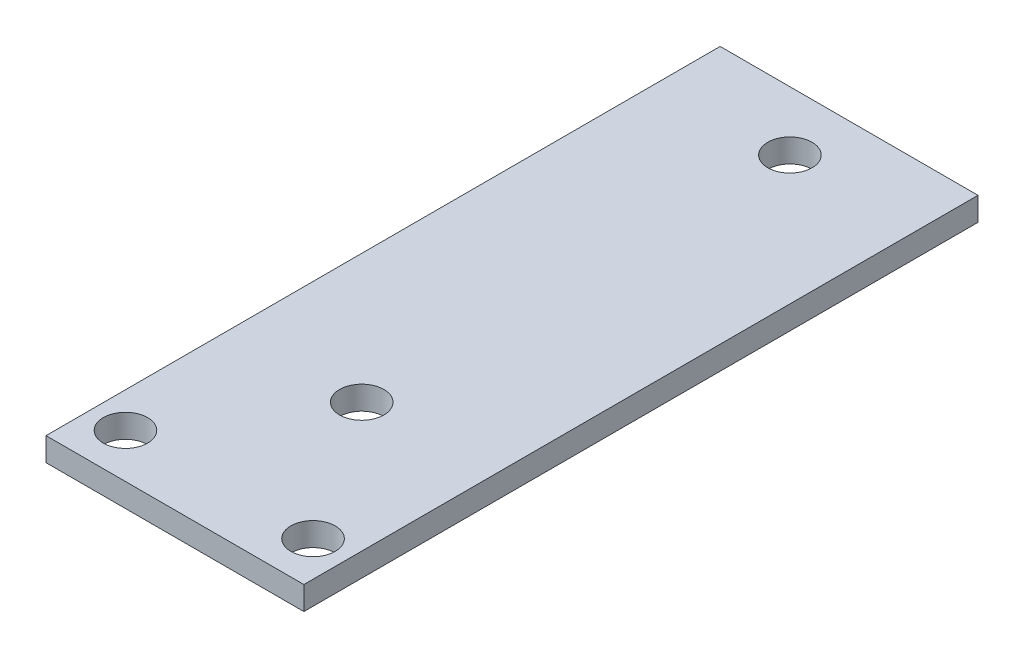
SolidWorks part; units mm, degrees
ref_plane "Front Plane" through (0, 0, 0) normal (0, 0, 1) x (1, 0, 0)
ref_plane "Top Plane" through (0, 0, 0) normal (0, 1, 0) x (1, 0, 0)
ref_plane "Right Plane" through (0, 0, 0) normal (1, 0, 0) x (0, 0, -1)
ref_plane "Plane1" through (0, -34.925, 0) normal (0, -1, 0) x (1, 0, 0)
sketch "Sketch1" plane through (0, -34.925, 0) normal (0, -1, 0) x (1, 0, 0)
  line L0 (-3.175, -115) -> (34.925, -115)
  line L1 (34.925, -115) -> (34.925, 5)
  line L2 (34.925, 5) -> (-3.175, 5)
  line L3 (-3.175, 5) -> (-3.175, -115)
extrude "Boss-Extrude1" add sketch "Sketch1" against normal blind 38.1
sketch "Sketch2" plane through (0, 0, -115) normal (0, 0, -1) x (-1, 0, 0)
  line L0 (-34.925, -34.925) -> (0, -34.925)
  line L1 (0, -34.925) -> (0, 0)
  line L2 (0, 0) -> (-34.925, 0)
  line L3 (-34.925, 0) -> (-34.925, -34.925)
extrude "Cut-Extrude1" cut sketch "Sketch2" against normal through all
sketch "Sketch18" plane through (0, 0, 5) normal (0, 0, 1) x (1, 0, 0)
  line L1 (-3.175, 3.175) -> (0, 3.175)
  line L2 (-3.175, 3.175) -> (-3.175, 0)
  line L3 (-3.175, 0) -> (0, 0)
  line L4 (0, 3.175) -> (0, 0)
extrude "Cut-Extrude3" cut sketch "Sketch18" against normal through all
sketch "Sketch19" plane through (0, 0, 0) normal (0, -1, 0) x (1, 0, 0)
  line L0 (17.4625, 5) -> (17.4625, -115) construction
  line L1 (0, 5) -> (34.925, 5) construction
  line L2 (0, -115) -> (34.925, -115) construction
  line L3 (17.4625, -6) -> (0, -6) construction
  line L4 (0, 5) -> (0, -115) construction
  line L5 (17.4625, -6) -> (34.925, -6) construction
  line L6 (34.925, 5) -> (34.925, -115) construction
  circle A0 centre (17.4625, -93.8) radius 3
  circle A1 centre (17.4625, -33.8) radius 3
  circle A3 centre (4.7625, -6) radius 3
  circle A4 centre (30.1625, -6) radius 3
  circle A5 centre (17.4625, -83.29) radius 3
  circle A6 centre (17.4625, -25.3) radius 3
  dimension "D1" = 6
  dimension "D2" = 6
  dimension "D3" = 12.7
  dimension "D4" = 21.2
  dimension "D6" = 12.7
  dimension "D5" = 81.2
  dimension "D7" = 6
  dimension "D8" = 6
  dimension "D9" = 109
  dimension "D12" = 6
  dimension "D13" = 6
  dimension "D10" = 31.71
  dimension "D11" = 89.7
extrude "Cut-Extrude4" cut sketch "Sketch19" against normal through all contours A4 | A3 | A6 | A5
sketch "Sketch20" plane through (0, 0, 0) normal (0, -1, 0) x (1, 0, 0)
  line L2 (0, 0) -> (34.925, 0)
  line L3 (0, 0) -> (34.925, 0)
  line L4 (0, 5) -> (34.925, 5)
  line L5 (0, 5) -> (0, 0)
  line L6 (0, 0) -> (34.925, 0)
  line L7 (34.925, 5) -> (34.925, 0)
  line M7 (34.925, -115) -> (34.925, 5)
  line M8 (34.925, 5) -> (0, 5)
  line M9 (0, 5) -> (0, -115)
  dimension "D1" = 5
extrude "Cut-Extrude5" cut sketch "Sketch20" against normal through all contours L3 M9 M7 M8 region at (17.4625, 0, 2.5)
sketch "Sketch21" plane through (0, 0, 0) normal (0, -1, 0) x (1, 0, 0)
  line L0 (0, -115) -> (34.925, -115) construction
  line L1 (0, -115) -> (34.925, -115)
  line L2 (0, -91.3) -> (34.925, -91.3)
  line L4 (0, -91.3) -> (34.925, -91.3)
  line L5 (0, -91.3) -> (0, -115)
  line L6 (0, -115) -> (34.925, -115)
  line L7 (34.925, -91.3) -> (34.925, -115)
  line M7 (0, 0) -> (0, -115)
  line M8 (0, -115) -> (34.925, -115)
  line M9 (34.925, -115) -> (34.925, 0)
  dimension "D1" = 23.7
extrude "Cut-Extrude6" cut sketch "Sketch21" against normal through all contours L2 M7 M8 M9 region at (17.4625, 0, -103.15)
